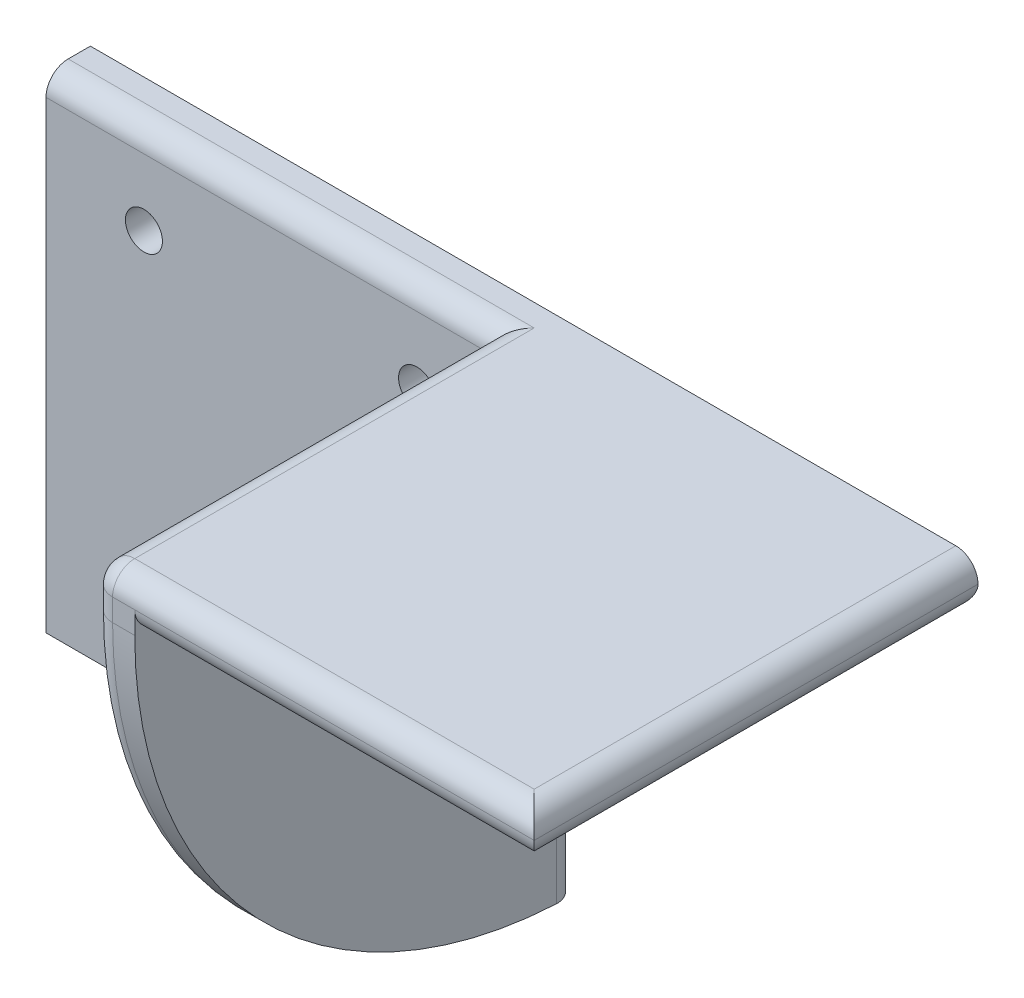
SolidWorks part; units mm, degrees
ref_plane "Спереди" through (0, 0, 0) normal (0, 0, 1) x (1, 0, 0)
ref_plane "Сверху" through (0, 0, 0) normal (0, 1, 0) x (1, 0, 0)
ref_plane "Справа" through (0, 0, 0) normal (1, 0, 0) x (0, 0, -1)
other "Configuration Table"
sketch "Эскиз1" plane through (0, 0, 0) normal (0, 1, 0) x (1, 0, 0)
  line L1 (-30, -30) -> (30, -30)
  line L2 (-30, -30) -> (-30, 30)
  line L3 (-30, 30) -> (30, 30)
  line L4 (30, -30) -> (30, 30)
  line L5 (0, 30) -> (0, -30) construction
  line L6 (-30, 0) -> (30, 0) construction
  point P0 (0, 0)
  dimension "D1" = 60
  dimension "D2" = 60
extrude "перемычка" add sketch "Эскиз1" along normal blind 6
sketch "Эскиз2" plane through (0, 0, 0) normal (0, -1, 0) x (1, 0, 0)
  line L0 (-30, -30) -> (-30, 30) construction
  line L1 (-30, 30) -> (-24, 30)
  line L2 (-30, 30) -> (-30, -30)
  line L3 (-30, -30) -> (-24, -30)
  line L4 (-24, 30) -> (-24, -30)
  line L5 (-27, -30) -> (-27, 30) construction
  line L6 (-30, 0) -> (-24, 0) construction
  line L7 (30, -30) -> (-30, -30) construction
  point P328 (-27, 0)
  dimension "D1" = 6
extrude "Бобышка-Вытянуть2" add sketch "Эскиз2" along normal blind 60
sketch "Эскиз3" plane through (-30, 0, 0) normal (-1, 0, 0) x (0, 0, 1)
  line L0 (30, -60) -> (-30, -60) construction
  line L1 (-30, 6) -> (-24, 6)
  line L2 (-30, 6) -> (-30, -60)
  line L3 (-30, -60) -> (-24, -60)
  line L4 (-24, 6) -> (-24, -60)
  line L5 (-27, -60) -> (-27, 6) construction
  line L6 (-30, -27) -> (-24, -27) construction
  point P360 (-27, -27)
  dimension "D1" = 6
extrude " к шкафу" add sketch "Эскиз3" along normal blind 60
fillet "Скругление1" radius 60 1 edges at (-27, -60, 30)
sketch "Эскиз4" plane through (0, 0, -24) normal (0, 0, 1) x (1, 0, 0)
  line L0 (-76.7612, 14.66) -> (-76.7612, -63.0729) construction
  line L1 (-39.8381, 13.8098) -> (-39.8381, -62.2227) construction
  line L2 (-96.4374, -5.9878) -> (-32.6721, -5.9878) construction
  line L3 (-95.3443, -53.5992) -> (-96.4374, -53.3563) construction
  line L4 (-96.4374, -53.3563) -> (-32.6721, -53.3563) construction
  circle A0 centre (-76.7612, -5.9878) radius 2.5
  circle A1 centre (-39.8381, -5.9878) radius 2.5
  circle A2 centre (-76.7612, -53.5992) radius 2.5
  circle A3 centre (-39.8381, -53.3563) radius 2.5
extrude "Вырез-Вытянуть1" cut sketch "Эскиз4" against normal blind 6
fillet "Скругление2" radius 3 1 edges at (-60, 6, -24)
fillet "Скругление3" radius 3 4 edges at (-24, -30, -30) (3, 0, -30) (30, 0, 0) (3, 0, 30)
fillet "Скругление4" radius 3 1 edges at (-30, 6, 1.5)
fillet "Скругление7" radius 3 5 edges at (-30, -40.2492, 14.4972) (-30, 1.5, 30) (-29.1213, 5.1213, 30) (30, 6, 0) (1.5, 6, 30)
